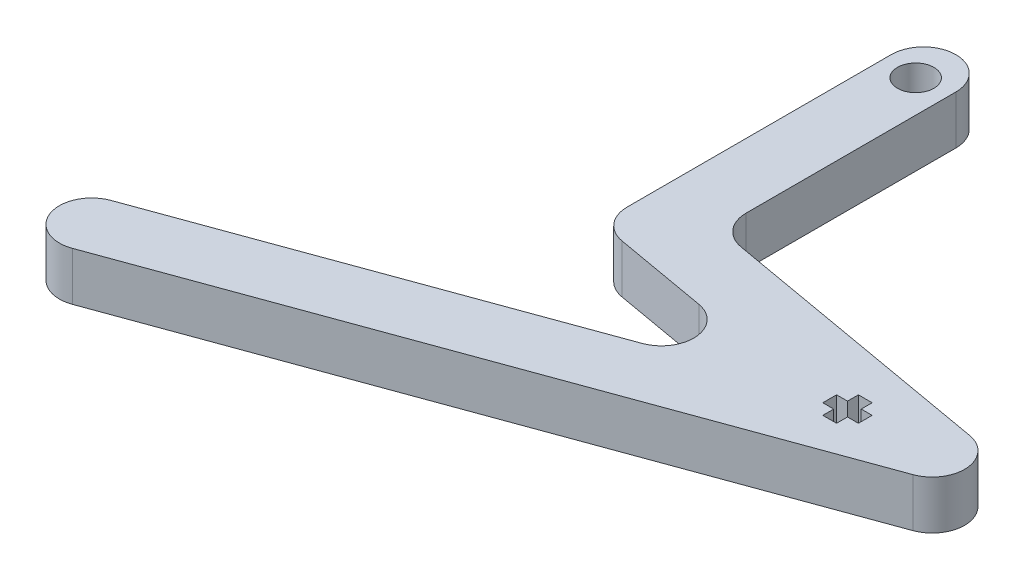
SolidWorks part; units mm, degrees
ref_plane "Front Plane" through (0, 0, 0) normal (0, 0, 1) x (1, 0, 0)
ref_plane "Top Plane" through (0, 0, 0) normal (0, 1, 0) x (1, 0, 0)
ref_plane "Right Plane" through (0, 0, 0) normal (1, 0, 0) x (0, 0, -1)
sketch "Sketch1" plane through (0, 0, 0) normal (0, 1, 0) x (1, 0, 0)
  line L16 (-71.479, 49.0484) -> (-71.479, 9.0484)
  line L19 (-63.479, 15.7612) -> (-63.479, 49.0484)
  line L22 (-63.479, 15.7612) -> (-11.1428, 6.533)
  line L26 (-71.479, 9.0484) -> (-41.9348, 3.839)
  line L27 (-41.9348, 3.839) -> (-107.8482, -20.1515)
  line L28 (-107.8482, -20.1515) -> (-105.1121, -27.6691)
  line L29 (-105.1121, -27.6691) -> (-11.1428, 6.533)
  line L30 (-71.479, 49.0484) -> (-63.479, 49.0484)
  line L43 (-38.433, 5.2517) -> (-38.433, 3.5517)
  line L44 (-38.433, 3.5517) -> (-37.083, 3.5517)
  line L45 (-37.083, 3.5517) -> (-37.083, 2.2017)
  line L46 (-37.083, 2.2017) -> (-35.383, 2.2017)
  line L47 (-35.383, 2.2017) -> (-35.383, 3.5517)
  line L48 (-35.383, 3.5517) -> (-34.033, 3.5517)
  line L49 (-34.033, 3.5517) -> (-34.033, 5.2517)
  line L50 (-34.033, 5.2517) -> (-35.383, 5.2517)
  line L51 (-35.383, 5.2517) -> (-35.383, 6.6017)
  line L52 (-35.383, 6.6017) -> (-37.083, 6.6017)
  line L53 (-37.083, 6.6017) -> (-37.083, 5.2517)
  line L54 (-37.083, 5.2517) -> (-38.433, 5.2517)
  circle A46 centre (-67.479, 44.0775) radius 2.25
  circle A47 centre (-36.233, 4.4017) radius 2.3585 construction
  point P0 (-36.233, 4.4017)
  point P44 (-67.479, 49.0484)
  dimension "D2" = 1.7
  dimension "D3" = 8
  dimension "D1" = 1.35
  dimension "D8" = 4.5
  dimension "D4" = 100
  dimension "D5" = 30
  dimension "D6" = 8
  dimension "D7" = 8
  dimension "D10" = 40
  dimension "D11" = 100
  dimension "D12" = 30
extrude "Boss-Extrude1" add sketch "Sketch1" along normal blind 6
fillet "Fillet1" radius 4 8 edges at (-63.479, 3, -15.7612) (-71.479, 3, -9.0484) (-105.1121, 3, 27.6691) (-107.8482, 3, 20.1515) (-41.9348, 3, -3.839) (-11.1428, 3, -6.533) (-63.479, 3, -49.0484) (-71.479, 3, -49.0484)
